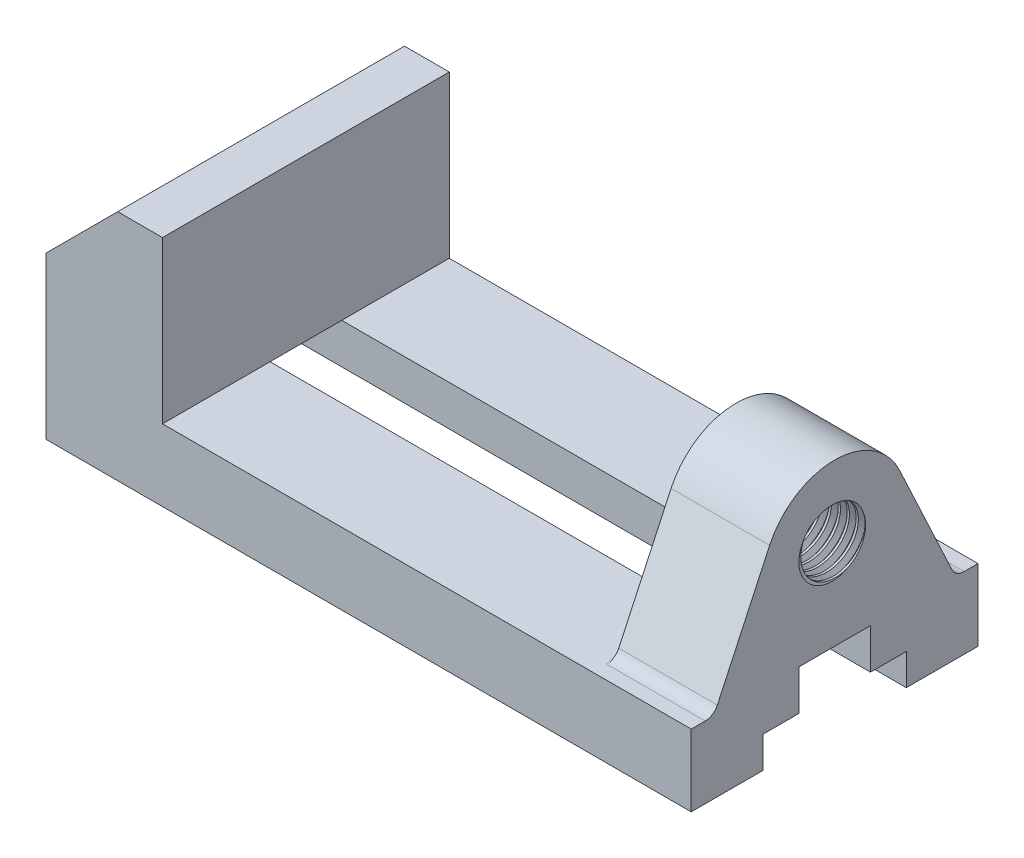
SolidWorks part; units mm, degrees
note: The reader was unsure of these and kept them because the rebuilt part matched: shared geometry of "Sketch3<4>", "Sketch3<5>".
ref_plane "Front Plane" through (0, 0, 0) normal (0, 0, 1) x (1, 0, 0)
ref_plane "Top Plane" through (0, 0, 0) normal (0, 1, 0) x (1, 0, 0)
ref_plane "Right Plane" through (0, 0, 0) normal (1, 0, 0) x (0, 0, -1)
sketch "Sketch1" plane through (0, 0, 0) normal (0, 1, 0) x (1, 0, 0)
  line L1 (-72, -32) -> (72, -32)
  line L2 (-72, -32) -> (-72, 32)
  line L3 (-72, 32) -> (72, 32)
  line L4 (72, -32) -> (72, 32)
  line L5 (-72, -32) -> (72, 32) construction
  line L6 (-72, 32) -> (72, -32) construction
  point P0 (0, 0)
  dimension "D1" = 144
  dimension "D2" = 64
extrude "Boss-Extrude1" add sketch "Sketch1" along normal blind 52
sketch "Sketch3" plane through (72, 0, 0) normal (1, 0, 0) x (0, 0, -1)
  line L0 (-32, 16) -> (32, 16) construction
  line L1 (-26.1725, 17.7321) -> (-14.5009, 42.7619)
  line L2 (14.5009, 42.7619) -> (26.1725, 17.7321)
  line L3 (0, 52) -> (0, 0) construction
  line L4 (-32, 0) -> (32, 0)
  line L5 (32, 0) -> (32, 52)
  line L6 (32, 52) -> (-32, 52)
  line L7 (-32, 52) -> (-32, 0)
  line L8 (-32, 0) -> (32, 0)
  line L9 (32, 0) -> (32, 52)
  line L10 (32, 52) -> (-32, 52)
  line L11 (-32, 52) -> (-32, 0)
  line L12 (0, 0) -> (-32, 26) construction
  line L13 (-32, 26) -> (32, 26) construction
  line L14 (-32, 36) -> (32, 36) construction
  line L15 (28.8914, 16) -> (32, 16)
  line L16 (-28.8914, 16) -> (-32, 16)
  line L17 (-16, 0) -> (-16, 7)
  line L18 (-16, 7) -> (-8, 7)
  line L19 (-8, 7) -> (-8, 16)
  line L20 (-8, 16) -> (8, 16)
  line L21 (16, 0) -> (16, 7)
  line L22 (16, 7) -> (8, 7)
  line L23 (8, 7) -> (8, 16)
  arc A0 (-26.1725, 17.7321) -> (-28.8914, 16) centre (-28.8914, 19) cw
  arc A1 (-14.5009, 42.7619) -> (14.5009, 42.7619) centre (0, 36) cw
  arc A2 (26.1725, 17.7321) -> (28.8914, 16) centre (28.8914, 19) ccw
  circle A3 centre (0, 36) radius 8
  point P30 (0, 16)
  line M18 (32, 52) -> (-32, 52)
  line M19 (-32, 52) -> (-32, 0)
  dimension "D4" = 16
  dimension "D5" = 50
  dimension "D6" = 3
  dimension "D7" = 3
  dimension "D11" = 16
  dimension "D2" = 16
  dimension "D3" = 16
  dimension "D8" = 16
  dimension "D9" = 8
  dimension "D10" = 7
  dimension "D1" = 0
extrude "Cut-Extrude1" cut sketch "Sketch3" against normal through all contours L22 L23 L20 L19 L18 L17 L8 L21
extrude "Cut-Extrude2" cut sketch "Sketch3<4>" against normal offset from surface (118 mm away) 26 contours L1 A1 L10 L16 A0 M19 | L2 A2 L15 L9 A1 M18 up to face at (-72, 13.6667, 0)
sketch "Sketch3<4>" plane through (72, 0, 0) normal (1, 0, 0) x (0, 0, -1) same geometry as "Sketch3"
extrude "Cut-Extrude3" cut sketch "Sketch3<5>" against normal blind 30 contours A3
sketch "Sketch3<5>" plane through (72, 0, 0) normal (1, 0, 0) x (0, 0, -1) same geometry as "Sketch3"
sketch "Sketch5" plane through (0, 0, 0) normal (0, 0, 1) x (1, 0, 0)
  line L0 (72, 52) -> (-46, 52) construction
  line L1 (72, 42.7619) -> (72, 52) construction
  line L2 (72, 17.7321) -> (72, 42.7619) construction
  line L3 (-46, 16) -> (72, 16) construction
  line L4 (-46, 16) -> (-46, 52) construction
  line L5 (72, 52) -> (-46, 52)
  line L6 (72, 42.7619) -> (72, 52)
  line L7 (72, 17.7321) -> (72, 42.7619)
  line L8 (-46, 16) -> (72, 16)
  line L9 (-46, 16) -> (-46, 52)
  line L10 (72, 16) -> (72, 17.7321) construction
  line L11 (72, 16) -> (72, 17.7321)
  line L12 (50, 52) -> (50, 16)
  dimension "D1" = 22
extrude "Cut-Extrude4" cut sketch "Sketch5" against normal through all both and the other way through all contours L12 L5 L9 L8
sketch "Sketch6" plane through (0, 0, -32) normal (0, 0, -1) x (-1, 0, 0)
  line L0 (72, 36) -> (56, 52)
  line L6 (46, 52) -> (46, 16)
  line L7 (46, 16) -> (-72, 16)
  line L8 (-72, 16) -> (-72, 0)
  line L9 (-72, 0) -> (72, 0)
  line L10 (72, 0) -> (72, 52)
  line L11 (72, 52) -> (46, 52)
  line L12 (46, 52) -> (46, 16)
  line L13 (46, 16) -> (-72, 16)
  line L14 (-72, 16) -> (-72, 0)
  line L15 (-72, 0) -> (72, 0)
  line L16 (72, 0) -> (72, 52)
  line L17 (72, 52) -> (46, 52)
  line M11 (72, 0) -> (72, 52)
  line M12 (72, 52) -> (46, 52)
  dimension "D2" = 16
  dimension "D3" = 16
  dimension "D1" = 0
extrude "Cut-Extrude5" cut sketch "Sketch6" against normal through all both contours L0 M11 M12
sketch "Sketch10" plane through (0, 0, 0) normal (0, -1, 0) x (-1, 0, 0)
  line L0 (72, 32) -> (72, 16) construction
  line L1 (-36, 22) -> (34, 22) construction
  line L3 (72, -32) -> (72, -16) construction
  line L4 (72, -16) -> (-72, -16) construction
  line L5 (-72, -16) -> (-72, -32) construction
  line L6 (-72, -32) -> (72, -32) construction
  line L7 (-72, 16) -> (72, 16) construction
  line L8 (72, 16) -> (72, 32) construction
  line L9 (72, 32) -> (-72, 32) construction
  line L10 (-72, 32) -> (-72, 16) construction
  line L11 (72, -32) -> (72, -16)
  line L12 (72, -16) -> (-72, -16)
  line L13 (-72, -16) -> (-72, -32)
  line L14 (-72, -32) -> (72, -32)
  line L15 (-72, 16) -> (72, 16)
  line L16 (72, 16) -> (72, 32)
  line L17 (72, 32) -> (-72, 32)
  line L18 (-72, 32) -> (-72, 16)
  line L20 (72, 0) -> (-72, 0) construction
  line L21 (72, -8) -> (72, 8) construction
  line L22 (-72, -8) -> (-72, 8) construction
  point P2 (34, 22)
  point P3 (-36, 22)
  point P18 (-36, -22)
  point P21 (34, -22)
  dimension "D1" = 38
  dimension "D2" = 70
  dimension "D3" = 22
hole_wizard "M6x1.0 Tapped Hole1" positions "3DSketch1" profile "Sketch11" tap size "M6x1.0" standard "ANSI Metric"
sketch3d "3DSketch1"
  point P0 (-34, 0, 22)
  point P3 (36, 0, 22)
  point P6 (-34, 0, -22)
  point P9 (36, 0, -22)
sketch "Sketch11" plane through (-34, 0, 22) normal (1, 0, 0) x (0, 0, -1)
  line L0 (0, 0) -> (0, 11.7321)
  line L1 (0, 11.7321) -> (3, 10)
  line L2 (3, 10) -> (3, 0.025)
  line L3 (3, 0.025) -> (3.025, 0)
  line L5 (3.025, 0) -> (0, 0)
  line L6 (-3, 0.025) -> (-3.025, 0) construction
  line L10 (0, 11.7321) -> (-3, 10) construction
  line L11 (0, -6.35) -> (0, 107.95) construction
  dimension "Tap Drill Dia." = 6
  dimension "Tap Drill Depth" = 10
  dimension "Near C'Sink Dia." = 6.05
  dimension "Near C'Sink Angle" = 90
  dimension "Drill Angle" = 120
cosmetic thread "Hole Thread1" parameters "D1"=12, "D2"=6
cosmetic thread "Hole Thread2" parameters "D1"=12, "D2"=6
cosmetic thread "Hole Thread3" parameters "D1"=12, "D2"=6
cosmetic thread "Hole Thread4" parameters "D1"=12, "D2"=6
thread "Thread1" [suppressed] pitch 2 start angle 0, offset 0, length 40, pitch 2, diameter 16
ref_plane "Plane1" through (72, 36, 8) normal (0, -1, 0) x (0, 0, 1)
sketch "Thread Profile1" plane through (72, 36, 8) normal (0, -1, 0) x (0, 0, 1)
  line L0 (0, 0) -> (0, 2) construction
  line L11 (0, 0) -> (0, 1.75)
  line L12 (0, 1.75) -> (-1.0825, 1.125)
  line L13 (-1.0825, 1.125) -> (-1.0825, 0.625)
  line L15 (-1.0825, 0.625) -> (0, 0)
  line L17 (-1.0825, 0.875) -> (0, 0.875) construction
  point P2 (0, 0)
  dimension "Pitch" = 2
  dimension "Profile_Angle" = 60
  dimension "Profile_Land" = 0.5
  dimension "Profile_Height" = 1.0825
thread "Thread2" pitch 2 start angle 0, offset 10, length 40, pitch 2, diameter 16
ref_plane "Plane2" through (82, 36, 8) normal (0, -1, 0) x (0, 0, 1)
sketch "Thread Profile2" plane through (82, 36, 8) normal (0, -1, 0) x (0, 0, 1)
  line L0 (0, 0) -> (0, 2) construction
  line L11 (0, 0) -> (0, 1.75)
  line L12 (0, 1.75) -> (-1.0825, 1.125)
  line L13 (-1.0825, 1.125) -> (-1.0825, 0.625)
  line L15 (-1.0825, 0.625) -> (0, 0)
  line L17 (-1.0825, 0.875) -> (0, 0.875) construction
  point P2 (0, 0)
  dimension "Pitch" = 2
  dimension "Profile_Angle" = 60
  dimension "Profile_Land" = 0.5
  dimension "Profile_Height" = 1.0825
